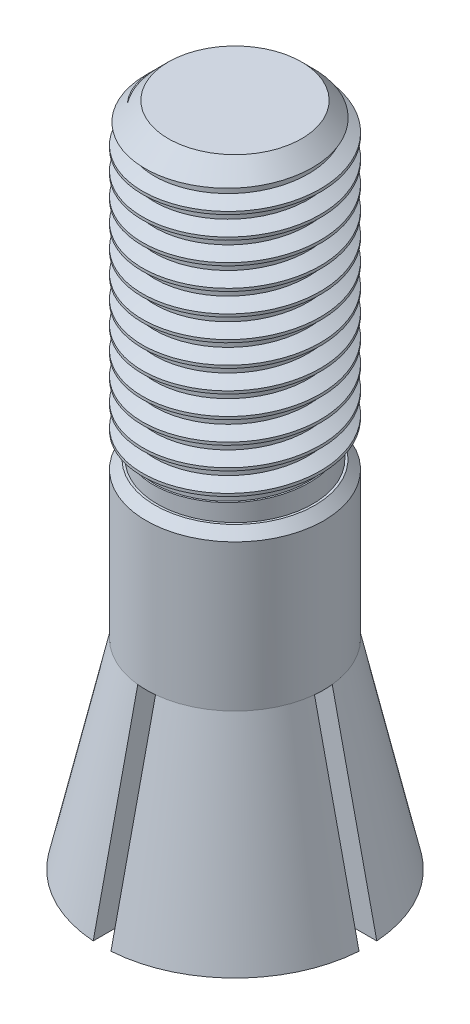
SolidWorks part; units mm, degrees
ref_plane "Front Plane" through (0, 0, 0) normal (0, 0, 1) x (1, 0, 0)
ref_plane "Top Plane" through (0, 0, 0) normal (0, 1, 0) x (1, 0, 0)
ref_plane "Right Plane" through (0, 0, 0) normal (1, 0, 0) x (0, 0, -1)
sketch "Sketch1" plane through (0, 0, 0) normal (0, 0, 1) x (1, 0, 0)
  line L0 (0, 0) -> (-1, 0) construction
  line L1 (-1, 0) -> (-3, 0)
  line L2 (-3, 0) -> (-2, 4.5)
  line L3 (-2, 4.5) -> (-2, 8)
  line L4 (-2, 8) -> (-1.75, 8)
  line L5 (-2, 15) -> (-2, 8.5)
  line L6 (-2, 15) -> (0, 15)
  line L7 (0, 15) -> (0, 6)
  line L8 (0, 6) -> (-1, 6)
  line L9 (-1, 6) -> (-1, 0)
  line L10 (-2, 8.5) -> (-1.75, 8.5)
  line L11 (-1.75, 8.5) -> (-1.75, 8)
  dimension "D9" = 0.25
  dimension "D1" = 6
  dimension "D2" = 4.5
  dimension "D3" = 3.5
  dimension "D4" = 15
  dimension "D5" = 1
  dimension "D6" = 3
  dimension "D7" = 2
  dimension "D8" = 2
  dimension "D10" = 6.5
revolve "Revolve1" add sketch "Sketch1" angle 360 about L7
sketch "Sketch2" plane through (0, 0, 0) normal (0, 0, 1) x (1, 0, 0)
  line L0 (-3, 0) -> (3, 0) construction
  line L1 (-0.2, 0) -> (0.2, 0)
  line L2 (-0.2, 0) -> (-0.2, 4.5)
  line L3 (-0.2, 4.5) -> (0.2, 4.5)
  line L4 (0.2, 0) -> (0.2, 4.5)
  line L5 (-2, 4.5) -> (2, 4.5) construction
  dimension "D1" = 0.4
extrude "Cut-Extrude1" cut sketch "Sketch2" against normal through all both and the other way through all
sketch "Sketch3" plane through (0, 0, 0) normal (1, 0, 0) x (0, 0, -1)
  line L0 (-2.9933, 0) -> (2.9933, 0) construction
  line L1 (-0.2, 0) -> (0.2, 0)
  line L2 (-0.2, 0) -> (-0.2, 4.5)
  line L3 (-0.2, 4.5) -> (0.2, 4.5)
  line L4 (0.2, 0) -> (0.2, 4.5)
  line L5 (-1.99, 4.5) -> (1.99, 4.5) construction
  dimension "D1" = 0.4
extrude "Cut-Extrude2" cut sketch "Sketch3" against normal through all both and the other way through all
chamfer "Chamfer1" distance 0.2 angle 45 1 edges at (-2, 8, 0)
chamfer "Chamfer2" distance 0.5 angle 45 1 edges at (-2, 15, 0)
thread "Thread1" pitch 0.5 method cut profile "Thread Profile1" start angle 0, offset 1, length 7, pitch 0.5, diameter 4
ref_plane "Plane1" through (-2, 15.5, 0) normal (0, 0, 1) x (-1, 0, 0)
sketch "Thread Profile1" plane through (-2, 15.5, 0) normal (0, 0, 1) x (-1, 0, 0)
  line L0 (0, 0) -> (0, 0.5) construction
  line L11 (0, 0) -> (0, 0.4375)
  line L12 (0, 0.4375) -> (-0.2706, 0.2812)
  line L13 (-0.2706, 0.2812) -> (-0.2706, 0.1562)
  line L15 (-0.2706, 0.1562) -> (0, 0)
  line L17 (-0.2706, 0.2187) -> (0, 0.2187) construction
  point P2 (0, 0)
  dimension "Pitch" = 0.5
  dimension "Profile_Angle" = 60
  dimension "Profile_Land" = 0.125
  dimension "Profile_Height" = 0.2706
